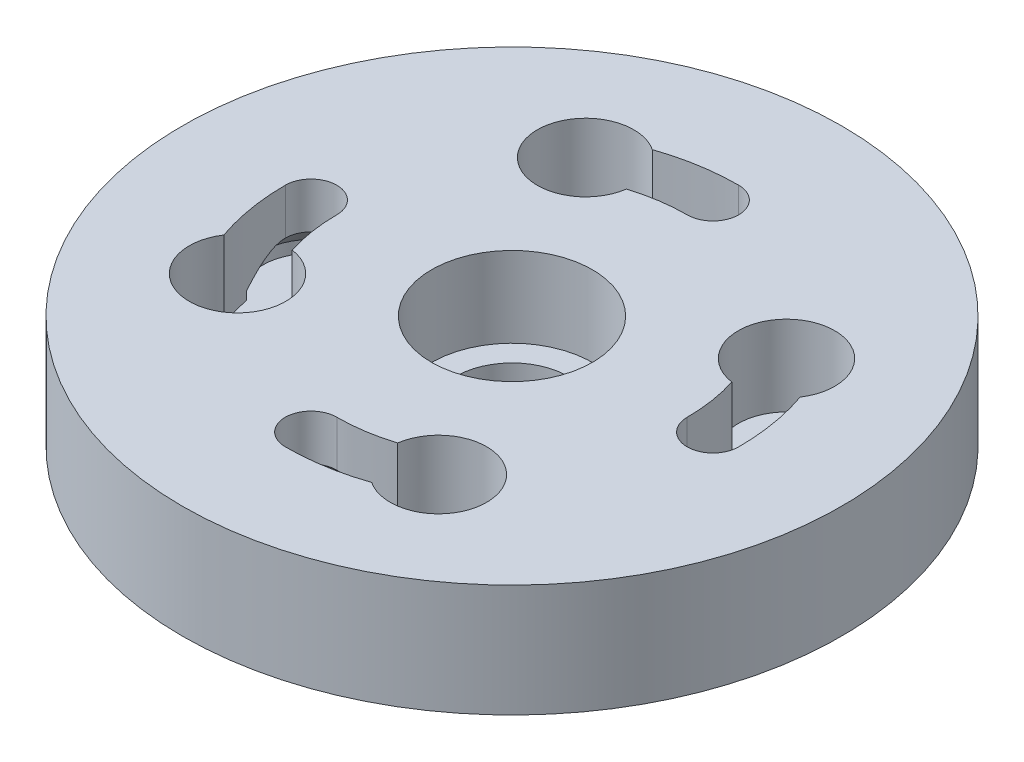
SolidWorks part; units mm, degrees
ref_plane "Front Plane" through (0, 0, 0) normal (0, 0, 1) x (1, 0, 0)
ref_plane "Top Plane" through (0, 0, 0) normal (0, 1, 0) x (1, 0, 0)
ref_plane "Right Plane" through (0, 0, 0) normal (1, 0, 0) x (0, 0, -1)
sketch "Sketch1" plane through (0, 0, 0) normal (0, 1, 0) x (1, 0, 0)
  circle A0 centre (0, 0) radius 17.5
  circle A1 centre (0, 0) radius 20.5
  dimension "D1" = 17.5
extrude "Boss-Extrude1" add sketch "Sketch1" along normal blind 7 contours A1
sketch "Sketch5" plane through (0, 7, 0) normal (0, 1, 0) x (1, 0, 0)
  circle A0 centre (0, 0) radius 3.5
  dimension "D1" = 7
extrude "Cut-Extrude4" cut sketch "Sketch5" against normal through all
sketch "Sketch6" plane through (0, 7, 0) normal (0, 1, 0) x (1, 0, 0)
  circle A0 centre (0, 0) radius 5
  dimension "D1" = 10
extrude "Cut-Extrude5" cut sketch "Sketch6" against normal blind 5
sketch "Sketch2" plane through (0, 7, 0) normal (0, 1, 0) x (1, 0, 0)
  line L0 (0, 0) -> (-6.25, 10.8253) construction
  line L1 (0, -3.85) -> (0, 3.85) construction
  circle A0 centre (-6.25, 10.8253) radius 3
  circle A1 centre (0, 12.5) radius 3 construction
  dimension "D1" = 6
  dimension "D2" = 30
  dimension "D3" = 12.5
  dimension "D4" = 12.5
extrude "Cut-Extrude1" cut sketch "Sketch2" against normal blind 5 contours A0
sketch "Sketch3" plane through (0, 2, 0) normal (0, 1, 0) x (1, 0, 0)
  arc A0 (-6.25, 10.8253) -> (0, 12.5) centre (0, 0) cw construction
  arc A1 (0, 14.1) -> (-7.05, 12.211) centre (0, 0) ccw
  arc A2 (0, 10.9) -> (-5.45, 9.4397) centre (0, 0) ccw
  arc A3 (0, 10.9) -> (0, 14.1) centre (0, 12.5) ccw
  arc A4 (-7.05, 12.211) -> (-5.45, 9.4397) centre (-6.25, 10.8253) ccw
  point P5 (-3.2352, 12.0741)
  dimension "D1" = 1.6
extrude "Cut-Extrude2" cut sketch "Sketch3" along normal through all
sketch "Sketch4" plane through (0, 2, 0) normal (0, 1, 0) x (1, 0, 0)
  arc A0 (-6.25, 10.8253) -> (0, 12.5) centre (0, 0) cw construction
  arc A1 (0, 15.5) -> (-7.75, 13.4234) centre (0, 0) ccw
  arc A2 (0, 9.5) -> (-4.75, 8.2272) centre (0, 0) ccw
  arc A3 (0, 9.5) -> (0, 15.5) centre (0, 12.5) ccw
  arc A4 (-7.75, 13.4234) -> (-4.75, 8.2272) centre (-6.25, 10.8253) ccw
  arc A6 (-4.5977, 13.3293) -> (-3.2811, 10.3944) centre (-6.25, 10.8253) ccw construction
  point P5 (-3.2352, 12.0741)
extrude "Cut-Extrude3" cut sketch "Sketch4" along normal blind 0.25
sketch "Sketch7" plane through (0, 2, 0) normal (0, 1, 0) x (1, 0, 0)
  circle A0 centre (0, 12.5) radius 3
  circle A1 centre (-6.25, 10.8253) radius 3
  circle A2 centre (-6.25, 10.8253) radius 3 construction
  dimension "D1" = 0
extrude "Cut-Extrude6" cut sketch "Sketch7" along normal blind 2.5
chamfer "Chamfer1" distance 1.75 angle 45 1 edges at (2.9844, 4.5, -12.8052)
pattern_circular "CirPattern1" count 4 over 360 about axis through (0, 7, 0) along (0, -1, 0) of "Chamfer1", "Cut-Extrude6", "Cut-Extrude3", "Cut-Extrude2", "Cut-Extrude1" reverse direction yes
equation "\"motor_r\"= 35 / 2mm"
equation "\"boru_d\"= 16mm"
equation "\"D1@Sketch1\"=\"motor_r\""
equation "\"D3@Sketch2\"=\"D4@Sketch2\""
